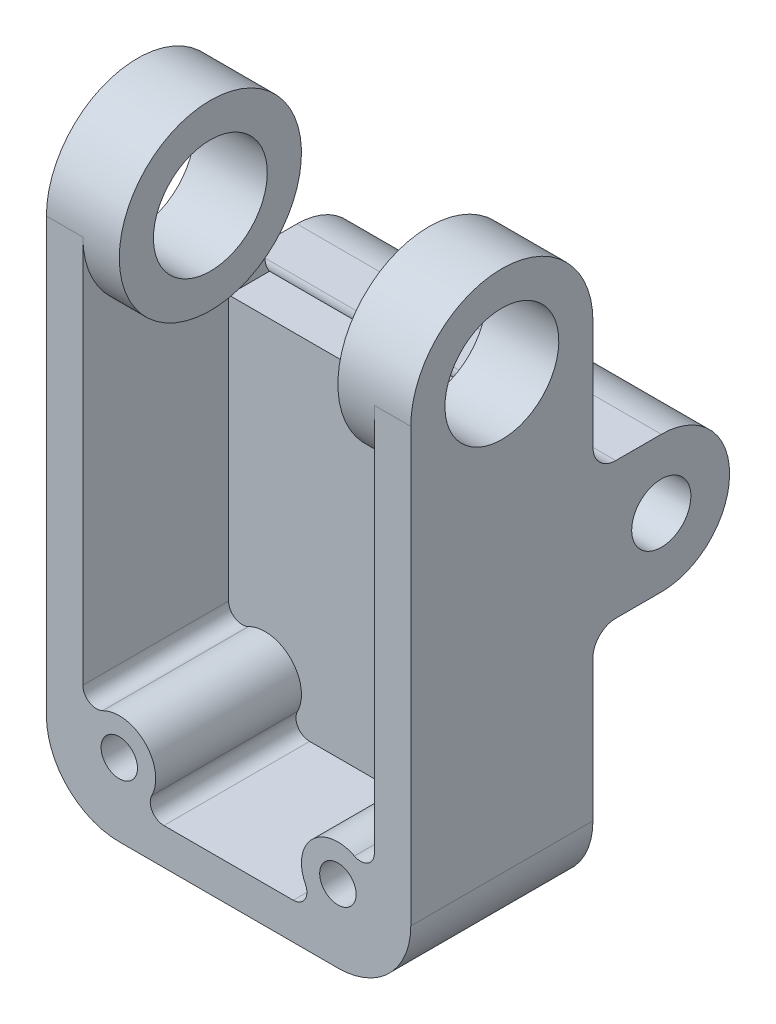
SolidWorks part; units mm, degrees
ref_plane "Front Plane" through (0, 0, 0) normal (1, 0, 0) x (0, 1, 0)
ref_plane "Top Plane" through (0, 0, 0) normal (0, 0, 1) x (0, 1, 0)
ref_plane "Right Plane" through (0, 0, 0) normal (0, 1, 0) x (-1, 0, 0)
sketch "Sketch1" plane through (0, 0, 0) normal (0, 0, 1) x (0, 1, 0)
  line L0 (0, -40) -> (0, 40)
  line L1 (0, 40) -> (84, 40)
  line L2 (84, 40) -> (84, -40)
  line L3 (84, -40) -> (0, -40)
  point P4 (0, 0)
  dimension "D1" = 84
  dimension "D2" = 80
extrude "Boss-Extrude1" add sketch "Sketch1" along normal blind 8
sketch "Sketch2" plane through (40, 0, 0) normal (1, 0, 0) x (0, 1, 0)
  line L0 (0, 0) -> (0, 40)
  line L1 (0, 40) -> (111, 40)
  line L6 (0, 0) -> (111, 0)
  arc A2 (111, 0) -> (111, 40) centre (111, 20) ccw
  circle A3 centre (111, 20) radius 12.5
  dimension "D2" = 111
  dimension "D3" = 25
  dimension "D1" = 40
extrude "Boss-Extrude3" add sketch "Sketch2" against normal blind 8
mirror "Mirror1" about plane through (0, 0, 0) normal (1, 0, 0) of "Boss-Extrude3"
sketch "Sketch3" plane through (0, 0, 0) normal (0, 0, 1) x (0, 1, 0)
  line L0 (0, 0) -> (25.2538, 0) construction
  line L1 (-22, 0) -> (22, 0) construction
  line L2 (0, 32) -> (0, -32) construction
  line L3 (111, 40) -> (0, 40) construction
  line L5 (8, 14.202) -> (8, -14.202)
  line L6 (25.798, 32) -> (84, 32)
  line L7 (111, 32) -> (0, 32) construction
  line L8 (84, 32) -> (84, 40)
  line L9 (84, 40) -> (16, 40)
  line L10 (0, 24) -> (0, -24)
  line L11 (16, -40) -> (84, -40)
  line L12 (111, -40) -> (0, -40) construction
  line L13 (84, -40) -> (84, -32)
  line L14 (111, -32) -> (0, -32) construction
  line L15 (84, -32) -> (25.798, -32)
  line L16 (84, -32) -> (84, 32) construction
  circle A0 centre (16, 24) radius 4
  circle A1 centre (16, -24) radius 4
  arc A2 (12.3636, 16.8742) -> (23.1258, 27.6364) centre (16, 24) ccw
  arc A3 (12.3636, -16.8742) -> (23.1258, -27.6364) centre (16, -24) cw
  arc A4 (25.798, -32) -> (23.1258, -27.6364) centre (25.798, -29) cw
  arc A5 (8, -14.202) -> (12.3636, -16.8742) centre (11, -14.202) ccw
  arc A6 (25.798, 32) -> (23.1258, 27.6364) centre (25.798, 29) ccw
  arc A7 (8, 14.202) -> (12.3636, 16.8742) centre (11, 14.202) cw
  arc A8 (0, -24) -> (16, -40) centre (16, -24) ccw
  arc A9 (16, 40) -> (0, 24) centre (16, 24) ccw
  point P37 (16, 32)
  point P42 (0, -40)
  point P45 (0, 40)
  point P46 (84, 32)
  dimension "D1" = 8
  dimension "D4" = 16
  dimension "D6" = 3
  dimension "D7" = 16
  dimension "D2" = 16
  dimension "D3" = 16
  dimension "D5" = 8
fillet "Fillet1" radius 16 2 edges at (-40, 0, 20) (40, 0, 20)
extrude "Boss-Extrude4" add sketch "Sketch3" along normal up to surface (40 mm away) up to face at (-36.4641, 59.7679, 40)
sketch "Sketch4" plane through (-32, 0, 0) normal (1, 0, 0) x (0, 1, 0)
  circle A0 centre (111, 20) radius 20
  circle A1 centre (111, 20) radius 12.5
extrude "Boss-Extrude5" add sketch "Sketch4" along normal blind 8
mirror "Mirror2" about plane through (0, 0, 0) normal (1, 0, 0) of "Boss-Extrude5"
sketch "Sketch5" plane through (40, 0, 0) normal (1, 0, 0) x (0, 1, 0)
  line L0 (111, 20) -> (111, 14.0266) construction
  line L1 (52, -15) -> (52, 0)
  line L2 (16, 0) -> (111, 0) construction
  line L3 (52, 0) -> (82, 0)
  line L4 (82, 0) -> (82, -15)
  circle A0 centre (67, -15) radius 6.5
  arc A1 (52, -15) -> (82, -15) centre (67, -15) ccw
  dimension "D1" = 13
  dimension "D4" = 30
  dimension "D2" = 35
  dimension "D3" = 44
extrude "Boss-Extrude6" add sketch "Sketch5" against normal up to surface (80 mm away) up to face at (-40, 68.5, 20)
fillet "Fillet2" radius 5 2 edges at (0, 52, 0) (0, 82, 0)
sketch "Sketch6" plane through (0, 0, 0) normal (0, -1, 0) x (1, 0, 0)
  circle A0 centre (0, 16) radius 16
  circle A1 centre (0, 16) radius 5
  point P3 (0, 0)
  dimension "D2" = 32
  dimension "D3" = 10
  dimension "D1" = 16
extrude "Boss-Extrude7" add sketch "Sketch6" along normal blind 8
